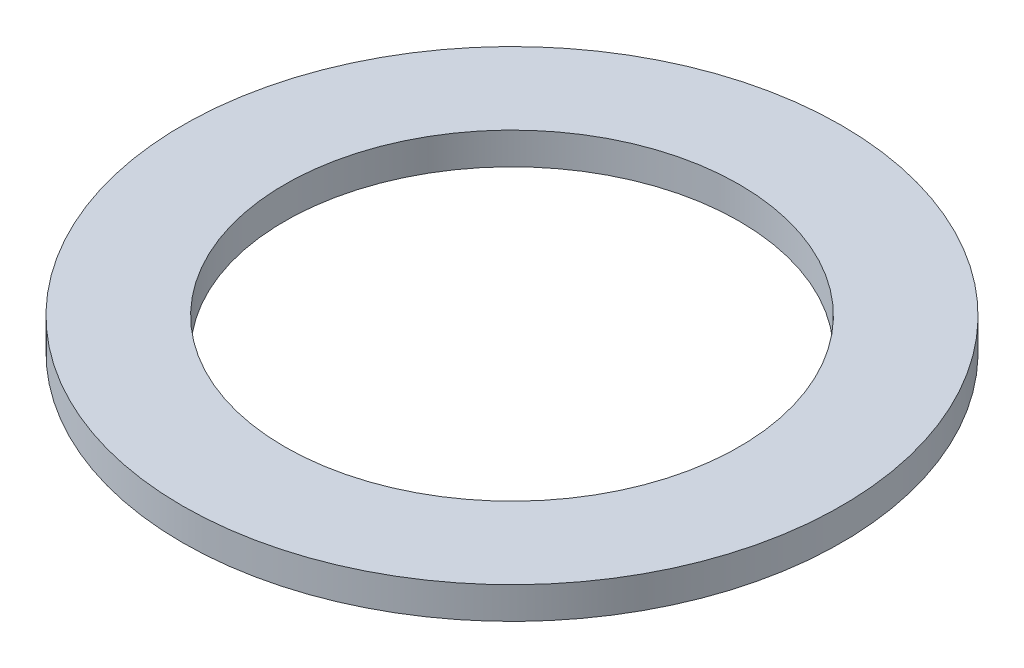
SolidWorks part; units mm, degrees
ref_plane "Front Plane" through (0, 0, 0) normal (0, 0, 1) x (1, 0, 0)
ref_plane "Top Plane" through (0, 0, 0) normal (0, 1, 0) x (1, 0, 0)
ref_plane "Right Plane" through (0, 0, 0) normal (1, 0, 0) x (0, 0, -1)
sketch "Sketch1" plane through (0, 0, 0) normal (0, 1, 0) x (1, 0, 0)
  circle A0 centre (0, 0) radius 72.5
  dimension "FLANGE_OD" = 145
extrude "Boss-Extrude1" add sketch "Sketch1" along normal blind 7
sketch "Sketch2" plane through (0, 0, 0) normal (0, 1, 0) x (1, 0, 0)
  circle A0 centre (0, 0) radius 50
  dimension "BORE_D" = 100
extrude "Cut-Extrude1" cut sketch "Sketch2" along normal through all
sketch "Sketch3" plane through (0, 7, 0) normal (0, 1, 0) x (1, 0, 0)
  circle A0 centre (0, 0) radius 33.3757 construction
  circle A1 centre (-33.3757, 0) radius 3.997
  dimension "BOLT_D" = 7.994
  dimension "BOLT_PCD" = 66.7514
extrude "Cut-Extrude2" cut sketch "Sketch3" against normal blind 5.315 rebuild error yes
pattern_circular "CirPattern1" count 4 over 360 rebuild error yes
